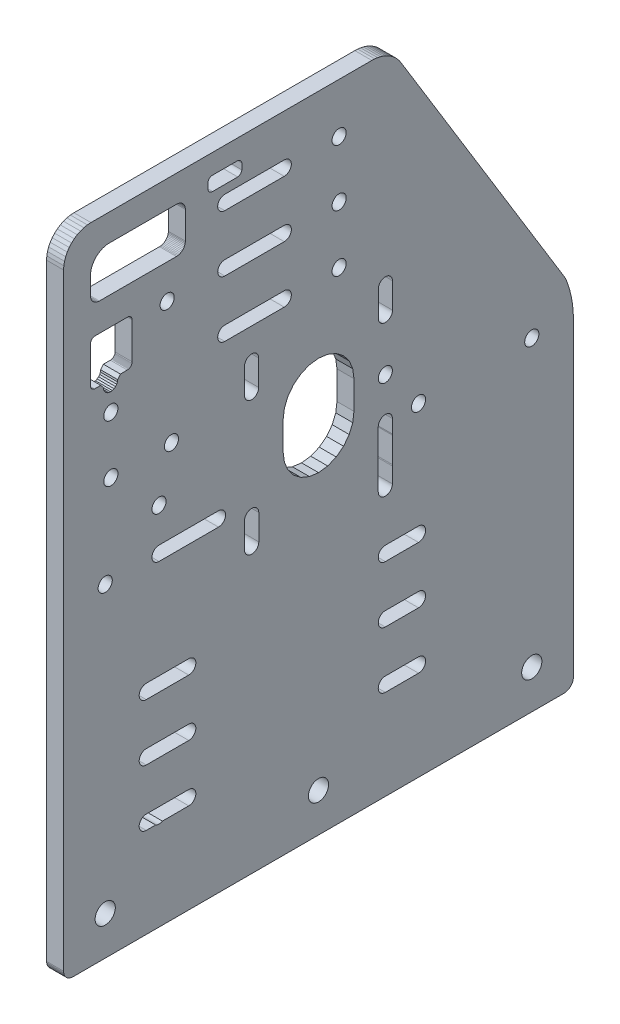
SolidWorks part; units mm, degrees
ref_plane "Front Plane" through (0, 0, 0) normal (0, 0, 1) x (1, 0, 0)
ref_plane "Top Plane" through (0, 0, 0) normal (0, 1, 0) x (1, 0, 0)
ref_plane "Right Plane" through (0, 0, 0) normal (1, 0, 0) x (0, 0, -1)
ref_plane "Plane1" through (0, 0, 0) normal (-1, 0, 0) x (0, -1, 0)
sketch "Sketch1" plane through (0, 0, 0) normal (-1, 0, 0) x (0, -1, 0)
  line L0 (-590.2121, -1614.2437) -> (-495.2304, -1672.3356)
  line L1 (-495.2304, -1672.3356) -> (-492.9855, -1673.1988)
  line L2 (-492.9855, -1673.1988) -> (-490.6881, -1673.9103)
  line L3 (-490.6881, -1673.9103) -> (-488.3483, -1674.4671)
  line L4 (-488.3483, -1674.4671) -> (-485.9766, -1674.8665)
  line L5 (-485.9766, -1674.8665) -> (-483.5835, -1675.1069)
  line L6 (-483.5835, -1675.1069) -> (-481.1798, -1675.1871)
  line L7 (-481.1798, -1675.1871) -> (-371.8266, -1675.1871)
  line L8 (-371.8266, -1675.1871) -> (-371.3877, -1675.1584)
  line L9 (-371.3877, -1675.1584) -> (-370.9562, -1675.0725)
  line L10 (-370.9562, -1675.0725) -> (-370.5397, -1674.9312)
  line L11 (-370.5397, -1674.9312) -> (-370.1452, -1674.7366)
  line L12 (-370.1452, -1674.7366) -> (-369.7795, -1674.4922)
  line L13 (-369.7795, -1674.4922) -> (-369.4487, -1674.2022)
  line L14 (-369.4487, -1674.2022) -> (-369.1587, -1673.8715)
  line L15 (-369.1587, -1673.8715) -> (-368.9143, -1673.5057)
  line L16 (-368.9143, -1673.5057) -> (-368.7198, -1673.1112)
  line L17 (-368.7198, -1673.1112) -> (-368.5784, -1672.6947)
  line L18 (-368.5784, -1672.6947) -> (-368.4926, -1672.2633)
  line L19 (-368.4926, -1672.2633) -> (-368.4638, -1671.8243)
  line L20 (-368.4638, -1671.8243) -> (-368.4638, -1498.5099)
  line L21 (-368.4638, -1498.5099) -> (-368.4926, -1498.071)
  line L22 (-368.4926, -1498.071) -> (-368.5784, -1497.6396)
  line L23 (-368.5784, -1497.6396) -> (-368.7198, -1497.223)
  line L24 (-368.7198, -1497.223) -> (-368.9143, -1496.8285)
  line L25 (-368.9143, -1496.8285) -> (-369.1587, -1496.4628)
  line L26 (-369.1587, -1496.4628) -> (-369.4487, -1496.1321)
  line L27 (-369.4487, -1496.1321) -> (-369.7795, -1495.842)
  line L28 (-369.7795, -1495.842) -> (-370.1452, -1495.5977)
  line L29 (-370.1452, -1495.5977) -> (-370.5397, -1495.4031)
  line L30 (-370.5397, -1495.4031) -> (-370.9562, -1495.2617)
  line L31 (-370.9562, -1495.2617) -> (-371.3877, -1495.1759)
  line L32 (-371.3877, -1495.1759) -> (-371.8266, -1495.1471)
  line L33 (-371.8266, -1495.1471) -> (-586.2881, -1495.1456)
  line L34 (-586.2881, -1495.1456) -> (-587.5497, -1495.2283)
  line L35 (-587.5497, -1495.2283) -> (-588.7897, -1495.475)
  line L36 (-588.7897, -1495.475) -> (-589.987, -1495.8813)
  line L37 (-589.987, -1495.8813) -> (-591.1209, -1496.4405)
  line L38 (-591.1209, -1496.4405) -> (-592.1721, -1497.1429)
  line L39 (-592.1721, -1497.1429) -> (-593.1227, -1497.9766)
  line L40 (-593.1227, -1497.9766) -> (-593.9563, -1498.9271)
  line L41 (-593.9563, -1498.9271) -> (-594.6588, -1499.9784)
  line L42 (-594.6588, -1499.9784) -> (-595.218, -1501.1123)
  line L43 (-595.218, -1501.1123) -> (-595.6244, -1502.3095)
  line L44 (-595.6244, -1502.3095) -> (-595.871, -1503.5495)
  line L45 (-595.871, -1503.5495) -> (-595.9537, -1504.8111)
  line L46 (-595.9537, -1504.8111) -> (-595.9537, -1603.9943)
  line L47 (-595.9537, -1603.9943) -> (-595.9102, -1605.016)
  line L48 (-595.9102, -1605.016) -> (-595.78, -1606.0302)
  line L49 (-595.78, -1606.0302) -> (-595.5641, -1607.0297)
  line L50 (-595.5641, -1607.0297) -> (-595.264, -1608.0073)
  line L51 (-595.264, -1608.0073) -> (-594.8819, -1608.9558)
  line L52 (-594.8819, -1608.9558) -> (-594.4205, -1609.8683)
  line L53 (-594.4205, -1609.8683) -> (-593.8833, -1610.7384)
  line L54 (-593.8833, -1610.7384) -> (-593.274, -1611.5596)
  line L55 (-593.274, -1611.5596) -> (-592.5971, -1612.3261)
  line L56 (-592.5971, -1612.3261) -> (-591.8575, -1613.0323)
  line L57 (-591.8575, -1613.0323) -> (-591.0606, -1613.673)
  line L58 (-591.0606, -1613.673) -> (-590.2121, -1614.2437)
  line L59 (-575.9778, -1552.0841) -> (-575.9778, -1573.0568)
  line L60 (-580.9777, -1573.098) -> (-580.9777, -1552.0841)
  line L61 (-535.9778, -1552.0854) -> (-535.9778, -1573.0582)
  line L62 (-540.9777, -1573.0993) -> (-540.9777, -1552.0854)
  line L63 (-555.9777, -1552.0992) -> (-555.9777, -1573.0855)
  line L64 (-560.9776, -1573.1131) -> (-560.9776, -1552.0992)
  line L65 (-524.9137, -1559.0552) -> (-515.9137, -1559.0552)
  line L66 (-515.9137, -1564.0552) -> (-524.9137, -1564.0552)
  line L67 (-524.9137, -1606.2991) -> (-515.9137, -1606.2991)
  line L68 (-515.9137, -1611.2991) -> (-524.9137, -1611.2991)
  line L69 (-477.6698, -1606.2991) -> (-468.6699, -1606.2991)
  line L70 (-468.6699, -1611.2991) -> (-477.6698, -1611.2991)
  line L71 (-477.6698, -1559.0528) -> (-468.6699, -1559.0552)
  line L72 (-468.6712, -1564.0782) -> (-477.6698, -1564.0758)
  line L73 (-586.0336, -1536.5791) -> (-586.215, -1536.2112)
  line L74 (-586.215, -1536.2112) -> (-586.3468, -1535.8228)
  line L75 (-586.3468, -1535.8228) -> (-586.4269, -1535.4204)
  line L76 (-586.4269, -1535.4204) -> (-586.4537, -1535.0111)
  line L77 (-586.4537, -1535.0111) -> (-586.4537, -1511.2962)
  line L78 (-586.4537, -1511.2962) -> (-586.3968, -1510.4284)
  line L79 (-586.3968, -1510.4284) -> (-586.2271, -1509.5753)
  line L80 (-586.2271, -1509.5753) -> (-585.9476, -1508.7517)
  line L81 (-585.9476, -1508.7517) -> (-585.5629, -1507.9717)
  line L82 (-585.5629, -1507.9717) -> (-585.0797, -1507.2485)
  line L83 (-585.0797, -1507.2485) -> (-584.5062, -1506.5946)
  line L84 (-584.5062, -1506.5946) -> (-583.8523, -1506.0211)
  line L85 (-583.8523, -1506.0211) -> (-583.1291, -1505.5379)
  line L86 (-583.1291, -1505.5379) -> (-582.3491, -1505.1533)
  line L87 (-582.3491, -1505.1533) -> (-581.5255, -1504.8737)
  line L88 (-581.5255, -1504.8737) -> (-580.6725, -1504.704)
  line L89 (-580.6725, -1504.704) -> (-579.8046, -1504.6471)
  line L90 (-579.8046, -1504.6471) -> (-573.6169, -1504.6471)
  line L91 (-573.6169, -1504.6471) -> (-573.2076, -1504.6739)
  line L92 (-573.2076, -1504.6739) -> (-572.8052, -1504.754)
  line L93 (-572.8052, -1504.754) -> (-572.4168, -1504.8858)
  line L94 (-572.4168, -1504.8858) -> (-572.0489, -1505.0673)
  line L95 (-572.0489, -1505.0673) -> (-571.7078, -1505.2952)
  line L96 (-571.7078, -1505.2952) -> (-571.3994, -1505.5656)
  line L97 (-571.3994, -1505.5656) -> (-571.1289, -1505.8741)
  line L98 (-571.1289, -1505.8741) -> (-570.901, -1506.2151)
  line L99 (-570.901, -1506.2151) -> (-570.7196, -1506.583)
  line L100 (-570.7196, -1506.583) -> (-570.5877, -1506.9715)
  line L101 (-570.5877, -1506.9715) -> (-570.5077, -1507.3738)
  line L102 (-570.5077, -1507.3738) -> (-570.4809, -1507.7831)
  line L103 (-570.4809, -1507.7831) -> (-570.4809, -1535.0111)
  line L104 (-570.4809, -1535.0111) -> (-570.5077, -1535.4204)
  line L105 (-570.5077, -1535.4204) -> (-570.5877, -1535.8228)
  line L106 (-570.5877, -1535.8228) -> (-570.7196, -1536.2112)
  line L107 (-570.7196, -1536.2112) -> (-570.901, -1536.5791)
  line L108 (-570.901, -1536.5791) -> (-571.1289, -1536.9202)
  line L109 (-571.1289, -1536.9202) -> (-571.3994, -1537.2286)
  line L110 (-571.3994, -1537.2286) -> (-571.7078, -1537.4991)
  line L111 (-571.7078, -1537.4991) -> (-572.0489, -1537.727)
  line L112 (-572.0489, -1537.727) -> (-572.4168, -1537.9084)
  line L113 (-572.4168, -1537.9084) -> (-572.8052, -1538.0403)
  line L114 (-572.8052, -1538.0403) -> (-573.2076, -1538.1203)
  line L115 (-573.2076, -1538.1203) -> (-573.6169, -1538.1471)
  line L116 (-573.6169, -1538.1471) -> (-583.3177, -1538.1471)
  line L117 (-583.3177, -1538.1471) -> (-583.727, -1538.1203)
  line L118 (-583.727, -1538.1203) -> (-584.1293, -1538.0403)
  line L119 (-584.1293, -1538.0403) -> (-584.5178, -1537.9084)
  line L120 (-584.5178, -1537.9084) -> (-584.8857, -1537.727)
  line L121 (-584.8857, -1537.727) -> (-585.2268, -1537.4991)
  line L122 (-585.2268, -1537.4991) -> (-585.5352, -1537.2286)
  line L123 (-585.5352, -1537.2286) -> (-585.8057, -1536.9202)
  line L124 (-585.8057, -1536.9202) -> (-586.0336, -1536.5791)
  line L125 (-560.5397, -1505.8783) -> (-560.4696, -1505.6715)
  line L126 (-560.4696, -1505.6715) -> (-560.373, -1505.4757)
  line L127 (-560.373, -1505.4757) -> (-560.2517, -1505.2942)
  line L128 (-560.2517, -1505.2942) -> (-560.1078, -1505.1301)
  line L129 (-560.1078, -1505.1301) -> (-559.9436, -1504.9862)
  line L130 (-559.9436, -1504.9862) -> (-559.7621, -1504.8649)
  line L131 (-559.7621, -1504.8649) -> (-559.5663, -1504.7683)
  line L132 (-559.5663, -1504.7683) -> (-559.3596, -1504.6981)
  line L133 (-559.3596, -1504.6981) -> (-559.1312, -1504.6471)
  line L134 (-559.1312, -1504.6471) -> (-558.9276, -1504.6413)
  line L135 (-558.9276, -1504.6413) -> (-548.4809, -1504.6452)
  line L136 (-548.4809, -1504.6452) -> (-545.8818, -1504.6452)
  line L137 (-545.8818, -1504.6452) -> (-545.6677, -1504.6877)
  line L138 (-545.6677, -1504.6877) -> (-545.461, -1504.7579)
  line L139 (-545.461, -1504.7579) -> (-545.2652, -1504.8545)
  line L140 (-545.2652, -1504.8545) -> (-545.0837, -1504.9758)
  line L141 (-545.0837, -1504.9758) -> (-544.9196, -1505.1197)
  line L142 (-544.9196, -1505.1197) -> (-544.7756, -1505.2838)
  line L143 (-544.7756, -1505.2838) -> (-544.6543, -1505.4654)
  line L144 (-544.6543, -1505.4654) -> (-544.5578, -1505.6612)
  line L145 (-544.5578, -1505.6612) -> (-544.4876, -1505.8679)
  line L146 (-544.4876, -1505.8679) -> (-544.445, -1506.082)
  line L147 (-544.445, -1506.082) -> (-544.4414, -1508.2677)
  line L148 (-544.4414, -1508.2677) -> (-543.221, -1509.2377)
  line L149 (-543.221, -1509.2377) -> (-542.574, -1509.3226)
  line L150 (-542.574, -1509.3226) -> (-541.9709, -1509.5721)
  line L151 (-541.9709, -1509.5721) -> (-541.453, -1509.9692)
  line L152 (-541.453, -1509.9692) -> (-541.0555, -1510.4868)
  line L153 (-541.0555, -1510.4868) -> (-540.8055, -1511.0897)
  line L154 (-540.8055, -1511.0897) -> (-540.72, -1511.7367)
  line L155 (-540.72, -1511.7367) -> (-540.805, -1512.3838)
  line L156 (-540.805, -1512.3838) -> (-541.0545, -1512.9868)
  line L157 (-541.0545, -1512.9868) -> (-541.4516, -1513.5047)
  line L158 (-541.4516, -1513.5047) -> (-541.9692, -1513.9022)
  line L159 (-541.9692, -1513.9022) -> (-542.572, -1514.1522)
  line L160 (-542.572, -1514.1522) -> (-543.219, -1514.2377)
  line L161 (-543.219, -1514.2377) -> (-544.4323, -1515.2077)
  line L162 (-544.4323, -1515.2077) -> (-544.4307, -1517.6776)
  line L163 (-544.4307, -1517.6776) -> (-544.4876, -1518.1096)
  line L164 (-544.4876, -1518.1096) -> (-544.5578, -1518.3163)
  line L165 (-544.5578, -1518.3163) -> (-544.6543, -1518.5121)
  line L166 (-544.6543, -1518.5121) -> (-544.7756, -1518.6936)
  line L167 (-544.7756, -1518.6936) -> (-544.9196, -1518.8578)
  line L168 (-544.9196, -1518.8578) -> (-545.0837, -1519.0017)
  line L169 (-545.0837, -1519.0017) -> (-545.2652, -1519.123)
  line L170 (-545.2652, -1519.123) -> (-545.461, -1519.2196)
  line L171 (-545.461, -1519.2196) -> (-545.6677, -1519.2897)
  line L172 (-545.6677, -1519.2897) -> (-546.0997, -1519.3486)
  line L173 (-546.0997, -1519.3486) -> (-558.9578, -1519.3427)
  line L174 (-558.9578, -1519.3427) -> (-559.1455, -1519.3427)
  line L175 (-559.1455, -1519.3427) -> (-559.3596, -1519.3001)
  line L176 (-559.3596, -1519.3001) -> (-559.5663, -1519.23)
  line L177 (-559.5663, -1519.23) -> (-559.7621, -1519.1334)
  line L178 (-559.7621, -1519.1334) -> (-559.9436, -1519.0121)
  line L179 (-559.9436, -1519.0121) -> (-560.1078, -1518.8682)
  line L180 (-560.1078, -1518.8682) -> (-560.2517, -1518.704)
  line L181 (-560.2517, -1518.704) -> (-560.373, -1518.5225)
  line L182 (-560.373, -1518.5225) -> (-560.4696, -1518.3267)
  line L183 (-560.4696, -1518.3267) -> (-560.5397, -1518.12)
  line L184 (-560.5397, -1518.12) -> (-560.5823, -1517.9059)
  line L185 (-560.5823, -1517.9059) -> (-560.5823, -1517.6796)
  line L186 (-560.5823, -1517.6796) -> (-560.568, -1506.084)
  line L187 (-560.568, -1506.084) -> (-560.5397, -1505.8783)
  line L188 (-512.6093, -1578.9371) -> (-510.6228, -1576.3483)
  line L189 (-510.6228, -1576.3483) -> (-508.034, -1574.3618)
  line L190 (-508.034, -1574.3618) -> (-505.0192, -1573.1131)
  line L191 (-505.0192, -1573.1131) -> (-501.784, -1572.6871)
  line L192 (-501.784, -1572.6871) -> (-491.784, -1572.6871)
  line L193 (-491.784, -1572.6871) -> (-488.5487, -1573.1131)
  line L194 (-488.5487, -1573.1131) -> (-485.534, -1574.3618)
  line L195 (-485.534, -1574.3618) -> (-482.9451, -1576.3483)
  line L196 (-482.9451, -1576.3483) -> (-480.9587, -1578.9371)
  line L197 (-480.9587, -1578.9371) -> (-479.7099, -1581.9519)
  line L198 (-479.7099, -1581.9519) -> (-479.284, -1585.1871)
  line L199 (-479.284, -1585.1871) -> (-479.7099, -1588.4224)
  line L200 (-479.7099, -1588.4224) -> (-480.9587, -1591.4371)
  line L201 (-480.9587, -1591.4371) -> (-482.9451, -1594.026)
  line L202 (-482.9451, -1594.026) -> (-485.534, -1596.0125)
  line L203 (-485.534, -1596.0125) -> (-488.5487, -1597.2612)
  line L204 (-488.5487, -1597.2612) -> (-491.784, -1597.6871)
  line L205 (-491.784, -1597.6871) -> (-501.784, -1597.6871)
  line L206 (-501.784, -1597.6871) -> (-505.0192, -1597.2612)
  line L207 (-505.0192, -1597.2612) -> (-508.034, -1596.0125)
  line L208 (-508.034, -1596.0125) -> (-510.6228, -1594.026)
  line L209 (-510.6228, -1594.026) -> (-512.6093, -1591.4371)
  line L210 (-512.6093, -1591.4371) -> (-513.858, -1588.4224)
  line L211 (-513.858, -1588.4224) -> (-514.284, -1585.1871)
  line L212 (-514.284, -1585.1871) -> (-513.858, -1581.9519)
  line L213 (-513.858, -1581.9519) -> (-512.6093, -1578.9371)
  line L214 (-588.9809, -1556.6482) -> (-588.9809, -1547.5504)
  line L215 (-587.544, -1546.1136) -> (-585.6436, -1546.0993)
  line L216 (-583.9746, -1547.7683) -> (-583.9889, -1556.6482)
  line L217 (-585.4257, -1558.085) -> (-587.544, -1558.085)
  arc A0 (-580.9777, -1552.0841) -> (-575.9778, -1552.0841) centre (-578.4777, -1552.0704) cw
  arc A1 (-575.9778, -1573.0568) -> (-580.9777, -1573.098) centre (-578.4777, -1573.0774) cw
  arc A2 (-540.9777, -1552.0854) -> (-535.9778, -1552.0854) centre (-538.4778, -1552.0718) cw
  arc A3 (-535.9778, -1573.0582) -> (-540.9777, -1573.0993) centre (-538.4778, -1573.0787) cw
  arc A4 (-560.9776, -1552.0992) -> (-555.9777, -1552.0992) centre (-558.4777, -1552.0856) cw
  arc A5 (-555.9777, -1573.0855) -> (-560.9776, -1573.1131) centre (-558.4777, -1573.0993) cw
  arc A6 (-515.9137, -1559.0552) -> (-515.9137, -1564.0552) centre (-515.9137, -1561.5552) cw
  arc A7 (-524.9137, -1564.0552) -> (-524.9137, -1559.0552) centre (-524.9137, -1561.5552) cw
  arc A8 (-515.9137, -1606.2991) -> (-515.9137, -1611.2991) centre (-515.9137, -1608.7991) cw
  arc A9 (-524.9137, -1611.2991) -> (-524.9137, -1606.2991) centre (-524.9137, -1608.7991) cw
  arc A10 (-468.6699, -1606.2991) -> (-468.6699, -1611.2991) centre (-468.6699, -1608.7991) cw
  arc A11 (-477.6698, -1611.2991) -> (-477.6698, -1606.2991) centre (-477.6698, -1608.7991) cw
  arc A12 (-468.6699, -1559.0552) -> (-468.6712, -1564.0782) centre (-468.6705, -1561.5667) cw
  arc A13 (-477.6698, -1564.0758) -> (-477.6698, -1559.0528) centre (-477.6692, -1561.5643) cw
  circle A14 centre (-382.1591, -1509.8471) radius 3.5685
  circle A15 centre (-382.1591, -1585.1671) radius 3.5685
  circle A16 centre (-382.1591, -1660.4871) radius 3.5685
  circle A17 centre (-538.3993, -1592.4578) radius 2.5
  circle A18 centre (-558.4485, -1592.4578) radius 2.5
  circle A19 centre (-578.4485, -1592.4578) radius 2.5
  circle A20 centre (-534.4436, -1511.8471) radius 2.5
  circle A21 centre (-558.4024, -1531.723) radius 2.5
  circle A22 centre (-514.4436, -1511.8471) radius 2.5
  circle A23 centre (-514.4436, -1533.239) radius 2.5
  circle A24 centre (-497.4962, -1528.8471) radius 2.5
  circle A25 centre (-482.7991, -1549.8471) radius 2.5
  circle A26 centre (-482.7991, -1509.8471) radius 2.5
  circle A27 centre (-482.7991, -1620.4871) radius 2.5
  circle A28 centre (-482.7991, -1660.4871) radius 2.5
  circle A29 centre (-402.4962, -1528.8471) radius 2.5
  arc A30 (-588.9809, -1547.5504) -> (-587.544, -1546.1136) centre (-587.3137, -1547.7807) cw
  arc A31 (-585.6436, -1546.0993) -> (-583.9746, -1547.7683) centre (-585.6436, -1547.7683) cw
  arc A32 (-583.9889, -1556.6482) -> (-585.4257, -1558.085) centre (-585.656, -1556.4179) cw
  arc A33 (-587.544, -1558.085) -> (-588.9809, -1556.6482) centre (-587.3262, -1556.4303) cw
  point P286 (0, 0)
extrude "Boss-Extrude1" add sketch "Sketch1" against normal blind 6
sketch "Sketch2" plane through (6, 0, 0) normal (1, 0, 0) x (0, 0, -1)
  line L0 (1549.8471, 482.7991) -> (1528.8471, 482.7962) construction
  line L3 (1608.7671, 482.7991) -> (1608.7671, 462.7991) construction
  line L4 (1611.2671, 482.7991) -> (1611.2671, 462.7991)
  line L5 (1606.2671, 482.7991) -> (1606.2671, 462.7991)
  line L6 (1620.4871, 442.7991) -> (1608.7671, 442.7991) construction
  line L7 (1620.4871, 440.2991) -> (1608.7671, 440.2991)
  line L8 (1620.4871, 445.2991) -> (1608.7671, 445.2991)
  line L9 (1620.4871, 422.7991) -> (1608.7671, 422.7991) construction
  line L10 (1620.4871, 420.2991) -> (1608.7671, 420.2991)
  line L11 (1620.4871, 425.2991) -> (1608.7671, 425.2991)
  line L12 (1620.4871, 402.7991) -> (1608.7671, 402.7991) construction
  line L13 (1620.4871, 400.2991) -> (1608.7671, 400.2991)
  line L14 (1620.4871, 405.2991) -> (1608.7671, 405.2991)
  line L15 (1539.3471, 442.7991) -> (1524.3471, 442.7991) construction
  line L24 (1539.3471, 440.2991) -> (1524.3471, 440.2991)
  line L31 (1539.3471, 445.2991) -> (1524.3471, 445.2991)
  line L34 (1539.3473, 422.7991) -> (1524.3473, 422.7991) construction
  line L39 (1549.8475, 480.2991) -> (1528.8475, 480.2962)
  line L40 (1549.8468, 485.2991) -> (1528.8468, 485.2962)
  line L41 (1539.3473, 420.2991) -> (1524.3473, 420.2991)
  line L42 (1539.3473, 425.2991) -> (1524.3473, 425.2991)
  line L43 (1539.3474, 402.7991) -> (1524.3474, 402.7991) construction
  line L44 (1539.3474, 400.2991) -> (1524.3474, 400.2991)
  line L45 (1539.3474, 405.2991) -> (1524.3474, 405.2991)
  circle A0 centre (1608.7671, 442.7991) radius 2.5 construction
  circle A26 centre (1620.4871, 402.7991) radius 2.5 construction
  circle A27 centre (1620.4871, 482.7991) radius 2.5 construction
  circle A28 centre (1549.8471, 482.7991) radius 2.5 construction
  circle A29 centre (1620.4871, 482.7991) radius 2.5
  circle A30 centre (1549.8471, 482.7991) radius 2.5 construction
  circle A40 centre (1620.4871, 442.7991) radius 2.5 construction
  circle A44 centre (1620.4871, 422.7991) radius 2.5 construction
  circle A52 centre (1608.7671, 422.7991) radius 2.5 construction
  circle A61 centre (1608.7671, 402.7991) radius 2.5 construction
  arc A62 (1611.2671, 482.7991) -> (1606.2671, 482.7991) centre (1608.7671, 482.7991) ccw
  arc A63 (1606.2671, 462.7991) -> (1611.2671, 462.7991) centre (1608.7671, 462.7991) ccw
  arc A64 (1611.2671, 482.7991) -> (1606.2671, 482.7991) centre (1608.7671, 482.7991) ccw
  arc A65 (1606.2671, 462.7991) -> (1611.2671, 462.7991) centre (1608.7671, 462.7991) ccw
  circle A66 centre (1528.8471, 497.4962) radius 2.5 construction
  circle A67 centre (1528.8471, 497.4962) radius 2.5
  circle A68 centre (1608.7671, 497.4962) radius 2.5
  circle A69 centre (1528.8471, 482.7962) radius 2.5 construction
  arc A76 (1620.4871, 440.2991) -> (1620.4871, 445.2991) centre (1620.4871, 442.7991) ccw
  arc A77 (1608.7671, 445.2991) -> (1608.7671, 440.2991) centre (1608.7671, 442.7991) ccw
  arc A78 (1620.4871, 420.2991) -> (1620.4871, 425.2991) centre (1620.4871, 422.7991) ccw
  arc A79 (1608.7671, 425.2991) -> (1608.7671, 420.2991) centre (1608.7671, 422.7991) ccw
  arc A80 (1620.4871, 400.2991) -> (1620.4871, 405.2991) centre (1620.4871, 402.7991) ccw
  arc A81 (1608.7671, 405.2991) -> (1608.7671, 400.2991) centre (1608.7671, 402.7991) ccw
  circle A92 centre (1539.3471, 442.7991) radius 4.3218 construction
  circle A93 centre (1549.8471, 442.7991) radius 2.5 construction
  circle A94 centre (1549.8471, 422.7991) radius 2.5 construction
  circle A105 centre (1620.4871, 462.7991) radius 2.5 [skipped]
  circle A106 centre (1549.8471, 462.7991) radius 2.5 [skipped]
  arc A107 (1549.8475, 480.2991) -> (1549.8468, 485.2991) centre (1549.8471, 482.7991) ccw
  arc A108 (1528.8468, 485.2962) -> (1528.8475, 480.2962) centre (1528.8471, 482.7962) ccw
  arc A109 (1539.3471, 440.2991) -> (1539.3471, 445.2991) centre (1539.3471, 442.7991) ccw
  arc A110 (1524.3471, 445.2991) -> (1524.3471, 440.2991) centre (1524.3471, 442.7991) ccw
  arc A111 (1539.3473, 420.2991) -> (1539.3473, 425.2991) centre (1539.3473, 422.7991) ccw
  arc A112 (1524.3473, 425.2991) -> (1524.3473, 420.2991) centre (1524.3473, 422.7991) ccw
  arc A113 (1539.3474, 400.2991) -> (1539.3474, 405.2991) centre (1539.3474, 402.7991) ccw
  arc A114 (1524.3474, 405.2991) -> (1524.3474, 400.2991) centre (1524.3474, 402.7991) ccw
  point P13 (1539.3471, 482.7976)
  point P19 (1608.7671, 472.7991)
  point P22 (1531.8471, 442.7991)
  point P40 (1531.8473, 422.7991)
  point P48 (1614.6271, 442.7991)
  point P54 (1561.5671, 472.7991)
  point P61 (1531.8474, 402.7991)
  point P80 (1614.6271, 422.7991)
  point P85 (1614.6271, 402.7991)
  dimension "D2" = 2.5
  dimension "D4" = 79.92
  dimension "D6" = 2.5
  dimension "D7" = 2
  dimension "D9" = 2
  dimension "D10" = 14.7
  dimension "D11" = 3
  dimension "D12" = 2
  dimension "D13" = 5
  dimension "D14" = 11.72
  dimension "D15" = 20
  dimension "D3" = 2
  dimension "D16" = 5
  dimension "D17" = 11.72
  dimension "D18" = 5
  dimension "D19" = 11.72
  dimension "D20" = 20
  dimension "D21" = 20
  dimension "D22" = 11.72
  dimension "D23" = 20
  dimension "D8" = 15
  dimension "D5" = 4
extrude "Cut-Extrude3" cut sketch "Sketch2" against normal through all contours L5 A63 L4 A62 | L24 | L45 A114 L44 A113 | L31 A110 L24 A109 | L42 A112 L41 A111 | A30 | A61 | A26 | A44 | A52 | A0 | A40 | A29 | A68 | A69 | L8 A77 L7 A76 | L11 A79 L10 A78 | L14 A81 L13 A80 | L40 A108 L39 A107 region at (6, 472.7991, -1608.7671) region at (6, 442.7991, -1531.8471) region at (6, 422.7991, -1531.8473) region at (6, 402.7991, -1531.8474)
